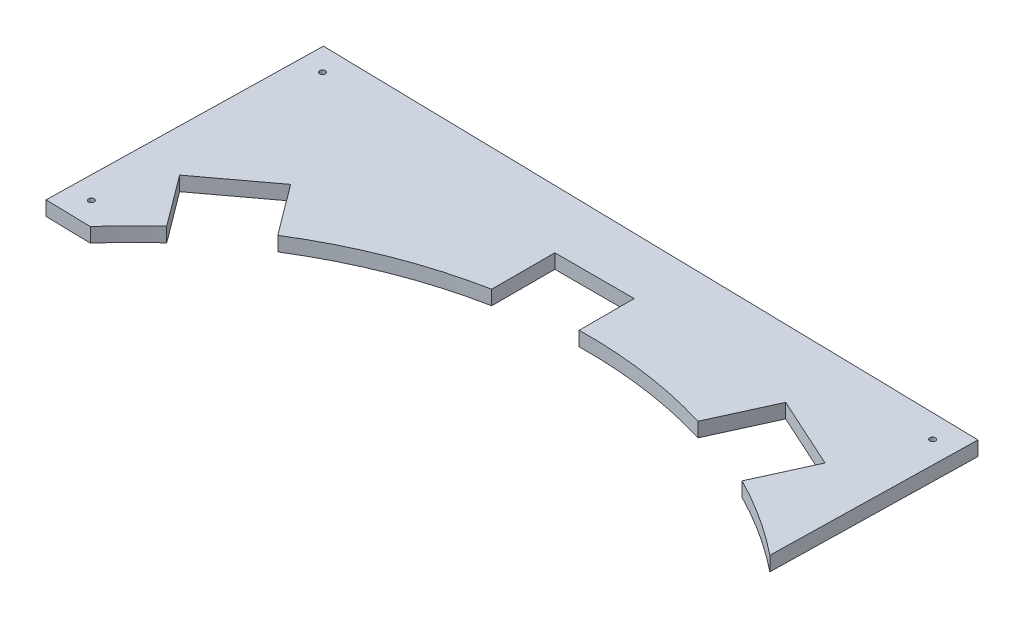
SolidWorks part; units mm, degrees
material "Balsa"
ref_plane "Front Plane" through (0, 0, 0) normal (0, 0, 1) x (1, 0, 0)
ref_plane "Top Plane" through (0, 0, 0) normal (0, 1, 0) x (1, 0, 0)
ref_plane "Right Plane" through (0, 0, 0) normal (1, 0, 0) x (0, 0, -1)
sketch "Sketch1" plane through (0, 0, 0) normal (0, 1, 0) x (1, 0, 0)
  line L0 (-12.8843, 57.5899) -> (-32.8801, 58.0016)
  line L5 (-32.8801, 58.0016) -> (-30.4097, 177.9762)
  line L6 (-30.4097, 177.9762) -> (264.5278, 171.9031)
  line L7 (264.5278, 171.9031) -> (262.6746, 81.9031)
  line L8 (99.6149, 122.2056) -> (99.6149, 150.073)
  line L9 (99.6149, 150.073) -> (134.6149, 150.073)
  line L10 (134.6149, 150.073) -> (134.6149, 125.8222)
  line L11 (195.598, 117.2478) -> (207.7139, 143.8488)
  line L12 (207.7139, 143.8488) -> (239.5656, 129.3413)
  line L13 (239.5656, 129.3413) -> (228.1093, 104.1884)
  line L14 (3.8471, 74.5464) -> (-12.8708, 96.9717)
  line L15 (-12.8708, 96.9717) -> (15.1898, 117.8906)
  line L16 (15.1898, 117.8906) -> (31.8184, 95.5852)
  arc A0 (-12.8843, 57.5899) -> (3.8471, 74.5464) centre (137.592, -74.1557) cw
  arc A1 (31.8184, 95.5852) -> (99.6149, 122.2056) centre (137.592, -74.1557) cw
  arc A2 (134.6149, 125.8222) -> (195.598, 117.2478) centre (137.592, -74.1557) cw
  arc A3 (228.1093, 104.1884) -> (262.6746, 81.9031) centre (137.592, -74.1557) cw
  circle A4 centre (-20.6177, 167.7724) radius 1.25
  circle A5 centre (254.3241, 162.1111) radius 1.25
  circle A6 centre (-22.6763, 67.7936) radius 1.25
  dimension "D5" = 200
  dimension "D11" = 2.5
  dimension "D14" = 2.5
  dimension "D17" = 2.5
  dimension "D1" = 295
  dimension "D2" = 20
  dimension "D3" = 120
  dimension "D4" = 90
  dimension "D6" = 35
  dimension "D7" = 35
  dimension "D8" = 35
  dimension "D9" = 10
  dimension "D10" = 10
  dimension "D12" = 10
  dimension "D13" = 10
  dimension "D15" = 10
  dimension "D16" = 10
extrude "Boss-Extrude1" add sketch "Sketch1" along normal blind 6.35
